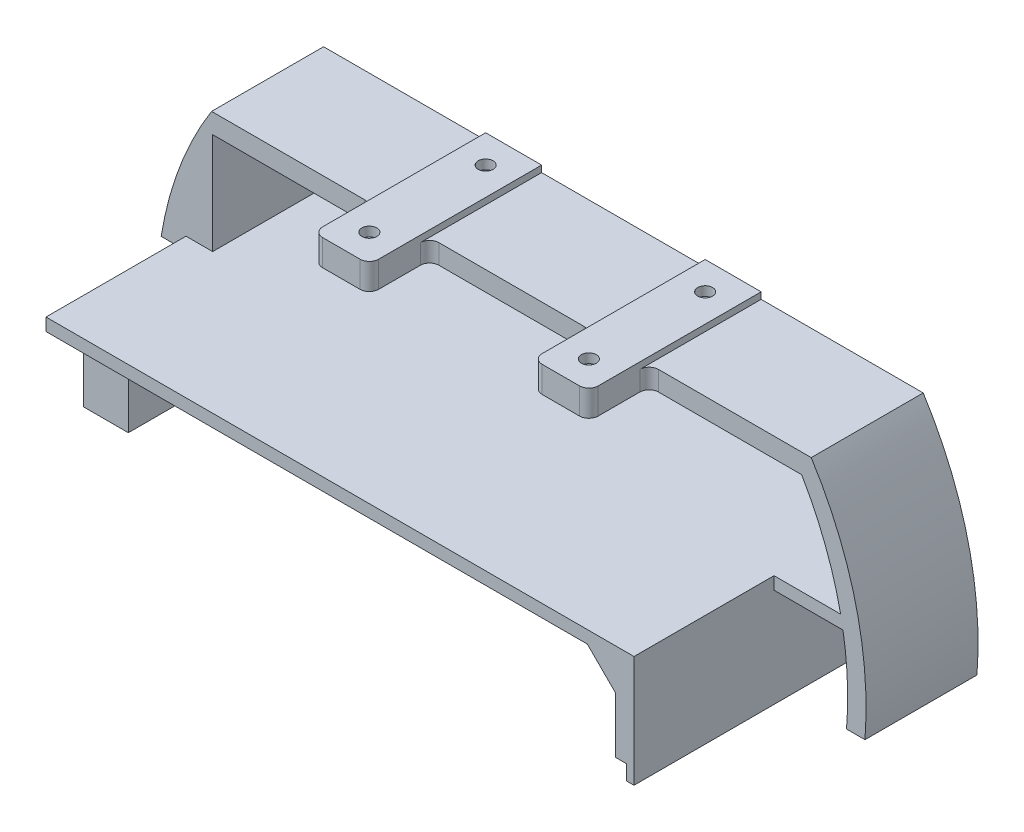
SolidWorks part; units mm, degrees
material "PET"
ref_plane "Front Plane" through (0, 0, 0) normal (0, 0, 1) x (1, 0, 0)
ref_plane "Top Plane" through (0, 0, 0) normal (0, 1, 0) x (1, 0, 0)
ref_plane "Right Plane" through (0, 0, 0) normal (1, 0, 0) x (0, 0, -1)
sketch "Sketch1" plane through (0, 0, 0) normal (0, 0, 1) x (1, 0, 0)
  line L0 (-19.5036, -13.8991) -> (-27.5713, -33.3763)
  line L1 (-39.8837, 22.352) -> (31.2363, 22.352)
  line L2 (-39.8837, 22.352) -> (-39.8837, 10.16)
  line L3 (-39.8837, 10.16) -> (31.2363, 10.16)
  line L4 (31.2363, 22.352) -> (31.2363, 10.16)
  line L5 (-44.5182, -3.81) -> (34.2218, -3.81)
  line L6 (-44.5182, -3.81) -> (-44.5182, -5.334)
  line L7 (-44.5182, -5.334) -> (34.2218, -5.334)
  line L8 (34.2218, -3.81) -> (34.2218, -5.334)
  line L9 (8.3138, -5.334) -> (33.7138, -5.334)
  line L10 (8.3138, -5.334) -> (8.3138, -11.684)
  line L11 (8.3138, -11.684) -> (33.7138, -11.684)
  line L12 (33.7138, -5.334) -> (33.7138, -11.684)
  line L13 (-42.4862, -3.81) -> (-22.1662, -3.81)
  line L14 (-42.4862, -3.81) -> (-42.4862, 7.62)
  line L15 (-42.4862, 7.62) -> (-22.1662, 7.62)
  line L16 (-22.1662, -3.81) -> (-22.1662, 7.62)
  line L17 (-44.5182, -5.334) -> (8.3138, -5.334)
  line L18 (-44.5182, -5.334) -> (-44.5182, -10.414)
  line L19 (-44.5182, -10.414) -> (8.3138, -10.414)
  line L20 (8.3138, -5.334) -> (8.3138, -10.414)
  line L22 (-27.5713, -33.3763) -> (-15.838, -38.2364)
  line L24 (-19.5036, -13.8991) -> (3.963, -23.6193)
  line L25 (-7.7703, -18.7592) -> (-15.838, -38.2364)
  line L28 (-15.838, -38.2364) -> (-4.1048, -43.0965)
  line L29 (3.963, -23.6193) -> (-4.1048, -43.0965)
  line L30 (0, 0) -> (-48.26, 0) construction
  line L31 (-21.59, 26.162) -> (21.59, 26.162)
  line L32 (0, 0) -> (-7.7703, -18.7592)
  line L33 (-21.59, 26.162) -> (-21.59, 38.862)
  line L34 (-21.59, 38.862) -> (21.59, 38.862)
  line L35 (21.59, 26.162) -> (21.59, 38.862)
  line L36 (0, 0) -> (0, 48.26) construction
  line L37 (-39.8837, 22.352) -> (-42.0994, 23.5938)
  line L39 (-44.5182, -10.414) -> (-46.9914, -10.9926) construction
  line L40 (0, 0) -> (0, -48.26) construction
  line L41 (-15.838, -38.2364) -> (-18.4683, -44.5864) construction
  circle A0 centre (0, 0) radius 48.26 construction
  circle A1 centre (-21.59, 21.59) radius 1.5875
  circle A2 centre (21.59, 21.59) radius 1.5875
  circle A3 centre (21.59, -21.59) radius 1.5875
  circle A4 centre (-21.59, -21.59) radius 1.5875
  dimension "D1" = 96.52
  dimension "D19" = 3.175
  dimension "D2" = 12.192
  dimension "D3" = 71.12
  dimension "D4" = 1.524
  dimension "D5" = 6.35
  dimension "D6" = 11.43
  dimension "D7" = 20.32
  dimension "D8" = 2.032
  dimension "D9" = 78.74
  dimension "D10" = 25.4
  dimension "D11" = 0.508
  dimension "D12" = 5.08
  dimension "D13" = 43.18
  dimension "D14" = 12.7
  dimension "D15" = 12.7
  dimension "D16" = 21.082
  dimension "D17" = 43.18
  dimension "D18" = 43.18
  dimension "D20" = 2.54
  dimension "D21" = 2.54
  dimension "D22" = 3.81
  dimension "D23" = 10.16
  dimension "D24" = 2.54
  dimension "D25" = 22.5
  dimension "D26" = 6.35
sketch "Sketch2" plane through (0, 0, 0) normal (0, 0, 1) x (1, 0, 0)
  line L0 (-41.7944, 24.13) -> (41.7944, 24.13)
  line L1 (-48.1094, -3.81) -> (48.1094, -3.81)
  line L3 (-44.5182, -3.81) -> (34.2218, -3.81) construction
  arc A0 (-41.7944, 24.13) -> (-48.1094, -3.81) centre (0, 0) ccw
  arc A1 (48.1094, -3.81) -> (41.7944, 24.13) centre (0, 0) ccw
  dimension "D1" = 27.94
extrude "Boss-Extrude1" add sketch "Sketch2" along normal blind 2.54
sketch "Sketch3" plane through (0, 0, 2.54) normal (0, 0, 1) x (1, 0, 0)
  line L0 (-39.8837, 10.16) -> (31.2363, 10.16) construction
  line L1 (-40.6457, 9.3345) -> (36.3163, 9.3345)
  line L2 (-40.6457, 9.3345) -> (-40.6457, 23.114)
  line L3 (-40.6457, 23.114) -> (36.3163, 23.114)
  line L4 (36.3163, 9.3345) -> (36.3163, 23.114)
  line L5 (-39.8837, 22.352) -> (-39.8837, 10.16) construction
  line L6 (-39.8837, 22.352) -> (31.2363, 22.352) construction
  line L7 (31.2363, 22.352) -> (31.2363, 10.16) construction
  dimension "D1" = 0.8255
  dimension "D2" = 0.762
  dimension "D3" = 0.762
  dimension "D4" = 5.08
extrude "Cut-Extrude1" cut sketch "Sketch3" against normal through all contours L3 L4 L1 L2
sketch "Sketch4" plane through (0, 0, 2.54) normal (0, 0, 1) x (1, 0, 0)
  line L0 (-22.1662, 7.62) -> (47.6546, 7.62)
  line L1 (-40.6457, 23.114) -> (36.3163, 23.114)
  line L2 (-40.6457, 23.114) -> (-40.6457, 9.3345)
  line L3 (-40.6457, 9.3345) -> (36.3163, 9.3345)
  line L5 (-22.1662, 7.62) -> (-47.6546, 7.62)
  line L6 (-41.7944, 24.13) -> (41.7944, 24.13)
  line L7 (36.3163, 9.3345) -> (44.7961, 9.3345)
  line L8 (36.3163, 23.114) -> (39.4913, 23.114)
  arc A0 (-41.7944, 24.13) -> (-48.1094, -3.81) centre (0, 0) ccw construction
  arc A1 (-41.7944, 24.13) -> (-47.6546, 7.62) centre (0, 0) ccw
  circle A2 centre (0, 0) radius 48.26 construction
  arc A3 (41.7944, 24.13) -> (47.6546, 7.62) centre (0, 0) cw
  arc A4 (44.7961, 9.3345) -> (39.4913, 23.114) centre (0, 0) ccw
  dimension "D1" = 3.175
extrude "Boss-Extrude2" add sketch "Sketch4" along normal blind 12.7
sketch "Sketch6" plane through (0, 7.62, 0) normal (0, -1, 0) x (1, 0, 0)
  line L0 (-47.6546, 15.24) -> (47.6546, 15.24) construction
  line L1 (-44.2764, 15.24) -> (35.7336, 15.24)
  line L2 (-44.2764, 15.24) -> (-44.2764, 34.29)
  line L3 (-44.2764, 34.29) -> (35.7336, 34.29)
  line L4 (35.7336, 15.24) -> (35.7336, 34.29)
  dimension "D1" = 34.29
  dimension "D2" = 80.01
  dimension "D3" = 3.3782
extrude "Boss-Extrude3" add sketch "Sketch6" against normal up to surface (1.7145 mm away) up to face at (13.4889, 9.3345, 5.9267)
sketch "Sketch8" plane through (0, 7.62, 0) normal (0, -1, 0) x (1, 0, 0)
  line L0 (-44.2764, 15.24) -> (-44.2764, 0) construction
  line L1 (48.26, 0) -> (-48.26, 0) construction
  line L2 (-39.4504, 0) -> (-39.4504, 19.05)
  line L3 (-44.2764, 0) -> (-39.4504, 0)
  line L4 (-44.2764, 0) -> (-44.2764, 29.1824)
  line L5 (-44.2764, 29.1824) -> (-38.1804, 29.1824)
  line L7 (7.2856, 0) -> (-0.3344, 0)
  line L8 (7.2856, 0) -> (7.2856, 6.35)
  line L9 (7.2856, 6.35) -> (-0.3344, 6.35)
  line L10 (-0.3344, 0) -> (-0.3344, 6.35)
  line L11 (-38.1804, 29.1824) -> (-38.1804, 22.5393)
  line L12 (-38.1804, 22.5393) -> (-39.4504, 19.05)
  line L20 (-44.5182, 0) -> (34.2218, 0) construction
  line L21 (35.7336, 34.29) -> (33.1936, 34.29)
  line L22 (35.7336, 34.29) -> (35.7336, 0)
  line L23 (35.7336, 0) -> (33.1936, 0)
  line L24 (33.1936, 34.29) -> (33.1936, 0)
  dimension "D1" = 29.21
  dimension "D2" = 4.826
  dimension "D3" = 43.942
  dimension "D4" = 7.62
  dimension "D5" = 6.35
  dimension "D6" = 19.05
  dimension "D7" = 6.096
  dimension "D8" = 160
  dimension "D9" = 2.54
extrude "Boss-Extrude4" add sketch "Sketch8" along normal up to surface (11.43 mm away) up to face at (0, -3.81, 1.27)
sketch "Sketch10" plane through (0, -3.81, 0) normal (0, -1, 0) x (1, 0, 0)
  line L0 (-48.1094, 0) -> (48.1094, 0) construction
  line L1 (35.7336, 34.29) -> (34.7176, 34.29)
  line L2 (35.7336, 34.29) -> (35.7336, 0)
  line L3 (35.7336, 0) -> (34.7176, 0)
  line L4 (34.7176, 34.29) -> (34.7176, 0)
  dimension "D1" = 1.016
extrude "Boss-Extrude5" add sketch "Sketch10" along normal blind 2.032
sketch "Sketch13" plane through (0, 24.13, 0) normal (0, 1, 0) x (1, 0, 0)
  line L0 (-14.9352, -3.81) -> (14.9352, -3.81) construction
  line L1 (14.9352, -3.81) -> (14.9352, -19.6342) construction
  line L2 (0, -3.81) -> (0, 0) construction
  line L3 (41.7944, 0) -> (-41.7944, 0) construction
  line L4 (-18.7452, 0) -> (-11.1252, 0)
  line L5 (-18.7452, 0) -> (-18.7452, -7.62)
  line L6 (-18.7452, -7.62) -> (-11.1252, -7.62) construction
  line L7 (-11.1252, 0) -> (-11.1252, -7.62)
  line L8 (-11.1252, -7.62) -> (-11.1252, -23.4442)
  line L9 (11.1252, 0) -> (18.7452, 0)
  line L10 (11.1252, 0) -> (11.1252, -23.4442)
  line L11 (11.1252, -23.4442) -> (18.7452, -23.4442)
  line L12 (18.7452, 0) -> (18.7452, -23.4442)
  line L13 (-11.1252, -23.4442) -> (-18.7452, -23.4442)
  line L14 (-18.7452, -23.4442) -> (-18.7452, -7.62)
  line L15 (-14.9352, -3.81) -> (-14.9352, -19.6342) construction
  line L16 (-14.9352, -19.6342) -> (14.9352, -19.6342) construction
  circle A0 centre (-14.9352, -3.81) radius 0.762
  circle A1 centre (14.9352, -19.6342) radius 0.762
  circle A2 centre (-14.9352, -19.6342) radius 0.762
  circle A3 centre (14.9352, -3.81) radius 0.762
  dimension "D1" = 1.524
  dimension "D2" = 1.524
  dimension "D3" = 29.8704
  dimension "D4" = 15.8242
  dimension "D5" = 3.81
  dimension "D6" = 3.81
  dimension "D7" = 3.81
  dimension "D8" = 3.81
  dimension "D9" = 3.81
  dimension "D10" = 3.81
  dimension "D11" = 3.81
extrude "Boss-Extrude6" add sketch "Sketch13" along normal blind 2.54
extrude "Boss-Extrude7" add sketch "Sketch13<2>" against normal up to surface (1.016 mm away) up to face at (11.7207, 23.114, 5.9267)
sketch "Sketch13<2>" plane through (0, 24.13, 0) normal (0, 1, 0) x (1, 0, 0) same geometry as "Sketch13"
extrude "Cut-Extrude2" cut sketch "Sketch13<3>" against normal up to next contours A0 | A3
sketch "Sketch13<3>" plane through (0, 24.13, 0) normal (0, 1, 0) x (1, 0, 0) same geometry as "Sketch13"
sketch "Sketch16" plane through (0, -3.81, 0) normal (0, -1, 0) x (1, 0, 0)
  circle A0 centre (-41.3173, 24.511) radius 0.762
  circle A1 centre (-41.3173, 3.429) radius 0.762
  circle A2 centre (2.6247, 3.429) radius 0.762
  point P0 (-41.3173, 24.511)
  point P1 (2.6247, 24.511)
  point P3 (2.6247, 3.429)
  point P5 (-41.3173, 3.429)
  dimension "D1" = 1.524
extrude "Cut-Extrude3" cut sketch "Sketch16" against normal blind 8.89
sketch "Sketch17" plane through (0, -3.81, 0) normal (0, -1, 0) x (1, 0, 0)
  circle A0 centre (-41.3173, 24.511) radius 1.016
  circle A1 centre (-41.3173, 3.429) radius 1.016
  circle A2 centre (2.6247, 3.429) radius 1.016
  dimension "D1" = 2.032
extrude "Cut-Extrude4" cut sketch "Sketch17" against normal blind 1.27
sketch "Sketch18" plane through (0, 26.67, 0) normal (0, 1, 0) x (1, 0, 0)
  circle A0 centre (-14.9352, -3.81) radius 1.016
  circle A1 centre (14.9352, -19.6342) radius 1.016
  circle A2 centre (-14.9352, -19.6342) radius 1.016
  circle A3 centre (14.9352, -3.81) radius 1.016
  dimension "D1" = 2.032
extrude "Cut-Extrude5" cut sketch "Sketch18" against normal blind 1.27
sketch "Sketch19" plane through (0, 0, 2.54) normal (0, 0, 1) x (1, 0, 0)
  line L0 (33.1936, 7.62) -> (33.1936, 3.81)
  line L1 (33.1936, -3.81) -> (33.1936, 7.62) construction
  line L2 (33.1936, 3.81) -> (29.3836, 7.62)
  line L3 (7.2856, 7.62) -> (33.1936, 7.62) construction
  line L4 (29.3836, 7.62) -> (33.1936, 7.62)
  dimension "D1" = 3.81
  dimension "D2" = 3.81
extrude "Boss-Extrude8" add sketch "Sketch19" along normal up to surface (31.75 mm away) up to face at (14.8421, 1.8256, 34.29)
sketch "Sketch20" plane through (-44.2764, 0, 0) normal (-1, 0, 0) x (0, 0, 1)
  line L0 (15.24, 7.62) -> (2.54, 7.62) construction
  line L1 (7.62, 7.62) -> (22.86, 7.62)
  line L2 (7.62, 7.62) -> (7.62, 5.08)
  line L3 (7.62, 5.08) -> (22.86, 5.08)
  line L4 (22.86, 7.62) -> (22.86, 5.08)
  line L5 (0, 24.13) -> (0, -3.81) construction
  dimension "D1" = 15.24
  dimension "D2" = 2.54
  dimension "D3" = 7.62
extrude "Cut-Extrude6" cut sketch "Sketch20" against normal up to next
sketch "Sketch21" plane through (0, 0, 2.54) normal (0, 0, 1) x (1, 0, 0)
  line L0 (35.7336, -3.81) -> (48.1094, -3.81) construction
  line L1 (44.7961, 9.3345) -> (47.6546, 7.62)
  line L2 (45.5994, -3.81) -> (48.1094, -3.81)
  line L3 (-48.1094, -3.81) -> (-44.2764, -3.81)
  line L4 (-44.2764, -3.81) -> (-44.2764, 7.62)
  line L5 (-44.2764, 7.62) -> (-47.6546, 7.62)
  line L6 (-48.1094, -3.81) -> (-44.2764, -3.81)
  line L7 (-44.2764, -3.81) -> (-44.2764, 7.62)
  line L8 (-44.2764, 7.62) -> (-47.6546, 7.62)
  arc A0 (48.1094, -3.81) -> (47.6546, 7.62) centre (0, 0) ccw construction
  arc A1 (-47.6546, 7.62) -> (-48.1094, -3.81) centre (0, 0) ccw
  arc A2 (-47.6546, 7.62) -> (-48.1094, -3.81) centre (0, 0) ccw
  arc A3 (48.1094, -3.81) -> (47.6546, 7.62) centre (0, 0) ccw
  arc A4 (45.5994, -3.81) -> (44.7961, 9.3345) centre (0, 0) ccw
  dimension "D1" = 0
extrude "Boss-Extrude9" add sketch "Sketch21" along normal up to surface (5.08 mm away) contours A2 L6 L7 L8 up to face at (-41.8634, 6.35, 7.62)
extrude "Boss-Extrude10" add sketch "Sketch21<3>" along normal up to surface (12.7 mm away) contours A3 L1 A4 L2 up to face at (35.5011, 16.1101, 15.24)
sketch "Sketch21<3>" plane through (0, 0, 2.54) normal (0, 0, 1) x (1, 0, 0) same geometry as "Sketch21"
sketch "Sketch23" plane through (0, 0, 0) normal (0, 0, -1) x (-1, 0, 0)
  line L0 (40.7967, 25.781) -> (18.7452, 25.781)
  line L2 (18.7452, 25.781) -> (18.7452, 24.13)
  line L3 (18.7452, 24.13) -> (41.7944, 24.13)
  line L5 (-11.1252, 24.13) -> (11.1252, 24.13)
  line L6 (-11.1252, 24.13) -> (-11.1252, 25.781)
  line L7 (-11.1252, 25.781) -> (11.1252, 25.781)
  line L8 (11.1252, 24.13) -> (11.1252, 25.781)
  line L9 (-40.7967, 25.781) -> (-18.7452, 25.781)
  line L10 (-18.7452, 26.67) -> (-18.7452, 24.13) construction
  line L11 (-18.7452, 25.781) -> (-18.7452, 24.13)
  line L12 (-18.7452, 24.13) -> (-41.7944, 24.13)
  arc A0 (-41.7944, 24.13) -> (-40.7967, 25.781) centre (0, 0) cw
  arc A1 (41.7944, 24.13) -> (40.7967, 25.781) centre (0, 0) ccw
  point P10 (18.7452, 25.4)
  point P20 (-40.5221, 26.1567)
  point P27 (41.035, 25.4)
  dimension "D1" = 1.651
extrude "Boss-Extrude11" add sketch "Sketch23" against normal up to surface (15.24 mm away) up to face at (-37.1924, 16.0831, 15.24)
fillet "Fillet1" radius 1.27 15 edges at (7.2856, 1.905, 6.35) (-0.3344, 1.905, 6.35) (-19.8924, 7.62, 2.54) (-41.2284, 5.08, 22.86) (-41.2284, 7.62, 22.86) (-41.8634, 5.08, 7.62) (-43.5525, 7.62, 7.62) (-18.7452, 24.4475, 15.24) (-18.7452, 24.892, 23.4442) (-11.1252, 24.892, 23.4442) (-11.1252, 24.4475, 15.24) (11.1252, 24.4475, 15.24) (11.1252, 24.892, 23.4442) (18.7452, 24.892, 23.4442) (18.7452, 24.4475, 15.24)
